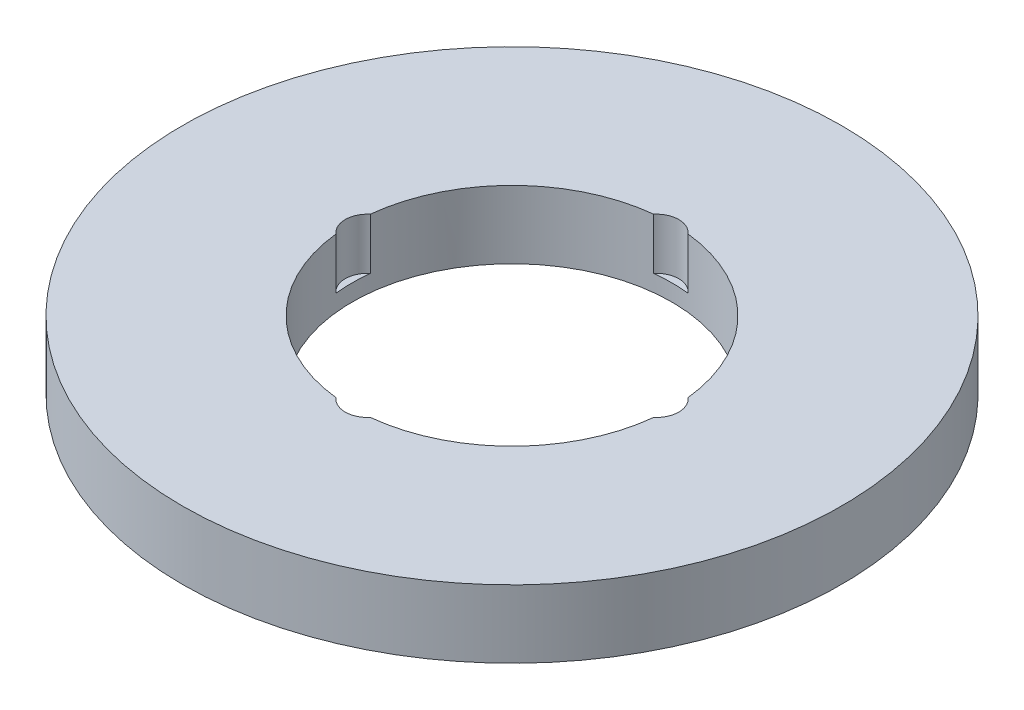
SolidWorks part; units mm, degrees
ref_plane "Front Plane" through (0, 0, 0) normal (0, 0, 1) x (1, 0, 0)
ref_plane "Top Plane" through (0, 0, 0) normal (0, 1, 0) x (1, 0, 0)
ref_plane "Right Plane" through (0, 0, 0) normal (1, 0, 0) x (0, 0, -1)
sketch "Sketch1" plane through (0, 0, 0) normal (0, 1, 0) x (1, 0, 0)
  circle A0 centre (0, 0) radius 82.5
  dimension "FLANGE_OD" = 165
extrude "Boss-Extrude1" add sketch "Sketch1" along normal blind 17
sketch "Sketch2" plane through (0, 0, 0) normal (0, 1, 0) x (1, 0, 0)
  circle A0 centre (0, 0) radius 40
  dimension "BORE_D" = 80
extrude "Cut-Extrude1" cut sketch "Sketch2" along normal through all
sketch "Sketch3" plane through (0, 17, 0) normal (0, 1, 0) x (1, 0, 0)
  circle A0 centre (0, 0) radius 36.0983 construction
  circle A1 centre (-36.0983, 0) radius 5.6525
  dimension "BOLT_D" = 11.305
  dimension "BOLT_PCD" = 72.1966
extrude "Cut-Extrude2" cut sketch "Sketch3" against normal blind 12.8392
pattern_circular "CirPattern1" count 4 over 360 about axis through (0, 0, 0) along (0, 1, 0) of "Cut-Extrude2"
